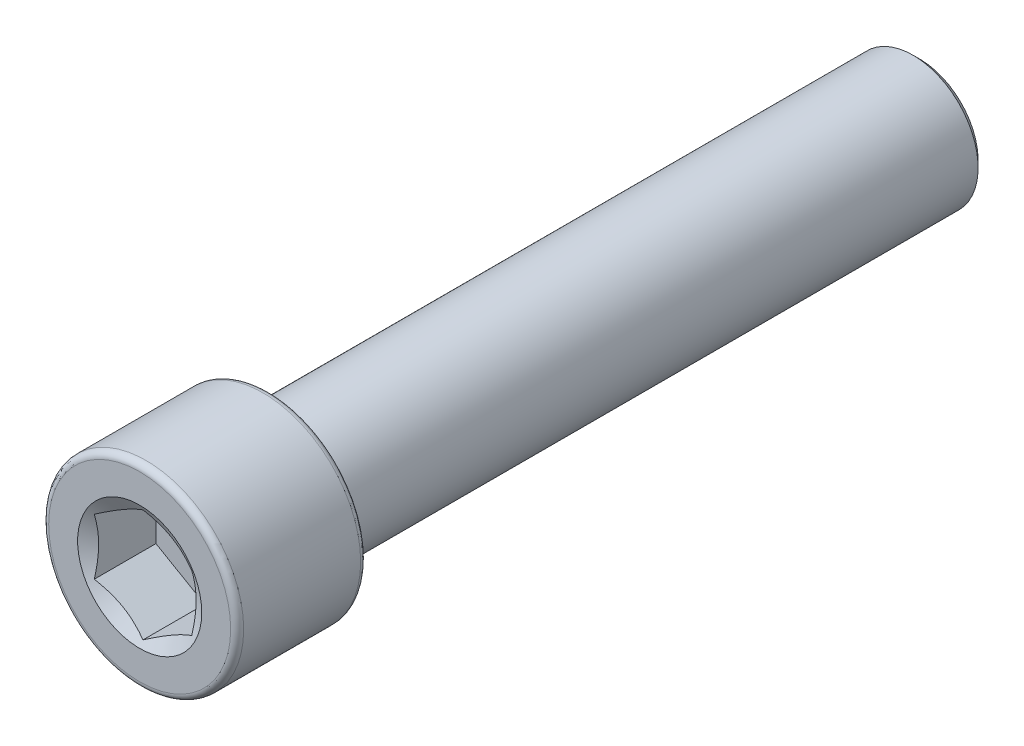
SolidWorks part; units mm, degrees
material "Cast Alloy Steel"
ref_plane "Front Plane" through (0, 0, 0) normal (0, 0, 1) x (1, 0, 0)
ref_plane "Top Plane" through (0, 0, 0) normal (0, 1, 0) x (1, 0, 0)
ref_plane "Right Plane" through (0, 0, 0) normal (1, 0, 0) x (0, 0, -1)
sketch "Sketch1" plane through (0, 0, 0) normal (1, 0, 0) x (0, 0, -1)
  line L0 (19.05, 0) -> (-19.05, 0) construction
  line L1 (-12.7, 4.7625) -> (-12.7, -4.7625) construction
  line L2 (19.05, 3.175) -> (19.05, -3.175) construction
  line L3 (18.9706, 3.3125) -> (19.6056, 2.2126) construction
  line L4 (19.5263, 2.3501) -> (19.685, 2.3501) construction
  line L5 (19.6056, 2.2126) -> (20.2406, 3.3125) construction
  line L6 (20.2406, 3.3125) -> (18.9706, 3.3125) construction
  line L7 (19.6056, 2.3501) -> (19.6056, 2.2126) construction
  line L8 (19.6056, 3.3125) -> (19.6056, 3.175) construction
  line L9 (20.1613, 3.175) -> (19.05, 3.175) construction
  point P4 (-12.7, 0)
  point P6 (-12.7, 2.3812)
  point P7 (14.605, -3.175)
  point P20 (19.6056, 3.2437)
  dimension "Head Height" = 6.35
  dimension "Head Diameter" = 9.525
  dimension "Drive Size" = 4.7625
  dimension "Length" = 31.75
  dimension "Screw Size Decimal Equivalent" = 6.35
  dimension "Pitch" = 1.27
  dimension "Pitch/8" = 0.1588
  dimension "Thread Note" = 4.445
sketch "Sketch2" plane through (0, 0, 0) normal (1, 0, 0) x (0, 0, -1)
  line L0 (19.05, 0) -> (19.05, 2.8575)
  line L1 (19.05, 3.175) -> (19.05, -3.175) construction
  line L2 (19.05, 2.8575) -> (18.7325, 3.175)
  line L3 (18.7325, 3.175) -> (-12.7, 3.175)
  line L4 (-12.7, 3.175) -> (-12.7, 4.445)
  line L5 (-13.0175, 4.7625) -> (-18.7325, 4.7625)
  line L6 (-19.05, 4.445) -> (-19.05, 0)
  line L7 (19.05, 0) -> (-19.05, 0) construction
  line L8 (-19.05, 0) -> (19.05, 0)
  arc A0 (-12.7, 4.445) -> (-13.0175, 4.7625) centre (-13.0175, 4.445) ccw
  arc A1 (-18.7325, 4.7625) -> (-19.05, 4.445) centre (-18.7325, 4.445) ccw
  point P19 (-12.7, 4.7625)
  dimension "D3" = 0.3175
  dimension "D1" = 0.3175
  dimension "D2" = 45
revolve "Revolve1" add sketch "Sketch2" angle 360 about L0
sketch "Sketch3" plane through (0, 0, 0) normal (0, 0, 1) x (1, 0, 0)
  line L1 (-2.3812, 1.3748) -> (-2.3812, -1.3748)
  line L2 (-2.3812, -1.3748) -> (0, -2.7496)
  line L3 (0, -2.7496) -> (2.3812, -1.3748)
  line L4 (2.3812, -1.3748) -> (2.3812, 1.3748)
  line L5 (2.3812, 1.3748) -> (0, 2.7496)
  line L6 (0, 2.7496) -> (-2.3812, 1.3748)
  circle A0 centre (0, 0) radius 2.3812 construction
  circle A1 centre (0, 0) radius 4.7625 construction
extrude "Cut-Extrude1" cut sketch "Sketch3" against normal blind 3.175 from vertex starting at point (0, 0, 19.05)
sketch "Sketch4" plane through (0, 0, 19.05) normal (0, 0, 1) x (1, 0, 0)
  line L0 (0, 2.7496) -> (0, 3.3148) construction
  line L1 (0, 3.3148) -> (0, 3.8799) construction
  line L2 (0, 3.8799) -> (0, 4.445) construction
  circle A0 centre (0, 0) radius 3.0322
  point P12 (0, 3.0322)
extrude "Cut-Extrude2" cut sketch "Sketch4" against normal through all draft 60
split "Split1" [suppressed] bodies to split 106 112
sketch "Sketch5" [suppressed] plane through (0, 0, 0) normal (1, 0, 0) x (0, 0, -1)
  line L0 (19.5263, 2.3501) -> (19.685, 2.3501)
  line L1 (19.685, 2.3501) -> (20.2009, 3.2437)
  line L2 (20.2009, 3.2437) -> (19.0103, 3.2437)
  line L3 (19.0103, 3.2437) -> (19.5263, 2.3501)
  line L4 (18.9706, 3.3125) -> (19.6056, 2.2126) construction
sketch "Sketch6" [suppressed] plane through (0, 0, -19.05) normal (0, 0, -1) x (-1, 0, 0)
  circle A0 centre (0, 0) radius 3.175
curve "Helix/Spiral1" [suppressed] pitch 1.27 height 33.02 turns 26
sweep "Cut-Sweep1" [suppressed] cut profiles "Sketch5" path "Helix/Spiral1"
sketch "Sketch7" [suppressed] plane through (0, 0, 12.7) normal (0, 0, -1) x (-1, 0, 0)
  circle A0 centre (0, 0) radius 3.2258
  circle A1 centre (0, 0) radius 3.175 construction
  dimension "D1" = 0.0508
extrude "Boss-Extrude1" [suppressed] add sketch "Sketch7" along normal through all draft 20 and the other way blind 0.635
ref_plane "Plane1" [suppressed] through (0, 0, 14.7955) normal (0, 0, -1) x (-1, 0, 0)
sketch "Sketch13" [suppressed] plane through (0, 0, 14.7955) normal (0, 0, -1) x (-1, 0, 0)
  line L0 (0.1191, 4.761) -> (0, 0) construction
  line L1 (0, 0) -> (-0.1191, 4.761) construction
  line L3 (0.1171, 4.6824) -> (0.1191, 4.761)
  line L6 (-0.1171, 4.6824) -> (-0.1191, 4.761)
  arc A1 (0.1191, 4.761) -> (-0.1191, 4.761) centre (0, 0) ccw
  circle A2 centre (0, 0) radius 4.7625 construction
  arc A3 (0.1171, 4.6824) -> (-0.1171, 4.6824) centre (0, 0) ccw
  point P2 (0, 4.7625)
  dimension "D3" = 0.0786
  dimension "D1" = 0.2381
extrude "Cut-Extrude3" [suppressed] cut sketch "Sketch13" against normal blind 3.5433
chamfer "Chamfer3" [suppressed] distance 0.0786 angle 60
chamfer "Chamfer4" [suppressed] distance 0.0786 angle 85
pattern_circular "CirPattern2" [suppressed] count 50 over 360 about axis through (0, 0, -19.05) along (0, 0, 1) of bodies 134
equation "\"Pitch/8@Sketch1\" = \"Pitch@Sketch1\" / 8"
equation "\"Thread Note@Sketch1\" = \"Pitch@Sketch1\" * 3.5"
equation "\"D1@Sketch2\"=\"Pitch@Sketch1\"*.25"
equation "\"D3@Sketch2\"=\"Head Height@Sketch1\"*.05"
equation "\"D1@Cut-Extrude1\" = \"Head Height@Sketch1\" * .5"
equation "\"D3@Helix/Spiral1\" = \"Length@Sketch1\" + \"Pitch@Sketch1\""
equation "\"D4@Helix/Spiral1\" = \"Pitch@Sketch1\""
equation "\"D2@Boss-Extrude1\" = \"Head Height@Sketch1\" * .1"
equation "\"D1\"= \"Screw Size Decimal Equivalent@Sketch1\" * .4"
equation "\"D1@Plane1\"=\"Head Height@Sketch1\" * .33"
equation "\"D1@Cut-Extrude3\"=( \"Head Height@Sketch1\" - \"D1@Plane1\" - \"D3@Sketch2\" )  * .9"
equation "\"D1@Chamfer3\"=\"D3@Sketch13\""
equation "\"D1@Chamfer4\"=\"D3@Sketch13\""
equation "\"D1@CirPattern2\"=( \"Head Diameter@Sketch1\" * pi )  /  ( 2.5*\"D1@Sketch13\" )"
equation "\"D1@Sketch13\"=\"Head Diameter@Sketch1\" * .025"
equation "\"D3@Sketch13\"=\"D1@Sketch13\"*.33"
